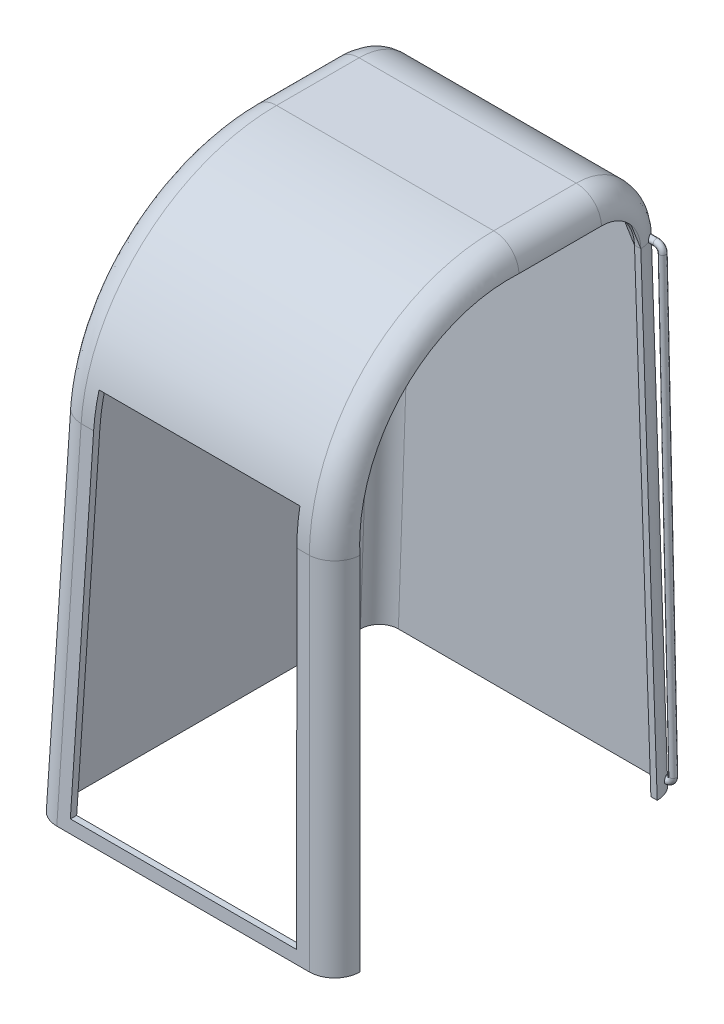
SolidWorks part; units mm, degrees
ref_plane "Front Plane" through (0, 0, 0) normal (0, 0, 1) x (1, 0, 0)
ref_plane "Top Plane" through (0, 0, 0) normal (0, 1, 0) x (1, 0, 0)
ref_plane "Right Plane" through (0, 0, 0) normal (1, 0, 0) x (0, 0, -1)
sketch "Sketch2" plane through (0, 0, 0) normal (0, 1, 0) x (1, 0, 0)
  line L1 (-533.4, -660.4) -> (533.4, -660.4)
  line L2 (-533.4, -660.4) -> (-533.4, 660.4)
  line L3 (-533.4, 660.4) -> (533.4, 660.4)
  line L4 (533.4, -660.4) -> (533.4, 660.4)
  line L5 (-533.4, -660.4) -> (533.4, 660.4) construction
  line L6 (-533.4, 660.4) -> (533.4, -660.4) construction
  point P0 (0, 0)
  dimension "D1" = 1320.8
  dimension "D2" = 1066.8
extrude "Boss-Extrude1" add sketch "Sketch2" along normal blind 2133.6
draft "Draft1" type of draft neutral plane draft angle 2 faces to draft 3 face at (533.4, 1066.8, 0) face at (-533.4, 1066.8, 0) face at (0, 1066.8, 660.4) neutral plane through (0, 2133.6, 0) neutral plane normal (0, 1, 0) parameters "D1"=2
fillet "Fillet3" radius 762 1 edges at (0, 2133.6, 660.4)
fillet "Fillet4" radius 254 1 edges at (0, 2133.6, -660.4)
fillet "Fillet5" radius 101.6 10 edges at (-583.494, 699.0967, 710.494) (-575.0884, 939.8, -660.4) (-535.9979, 2059.2051, -586.0051) (-533.4, 2133.6, -240.9274) (575.0884, 939.8, -660.4) (535.9979, 2059.2051, -586.0051) (533.4, 2133.6, -240.9274) (583.494, 699.0967, 710.494) (-540.8683, 1919.7369, 453.8748) (540.8683, 1919.7369, 453.8748)
shell "Shell2" thickness 25.4 removed face at (0, 0, 37.2676)
sketch "Sketch7" plane through (607.1665, 21.2027, 0) normal (0.9994, 0.0349, 0) x (0, 0, -1)
  line L0 (-584.5429, 1377.83) -> (-633.3688, -21.2156)
  line L1 (-633.3688, -21.2156) -> (558.8, -21.2156)
  line L2 (558.8, -21.2156) -> (558.8, 1863.078)
  line L3 (75.4548, 2015.5709) -> (406.4, 2015.5709)
  arc A0 (75.4548, 2015.5709) -> (-584.5429, 1377.83) centre (39.2865, 1392.6154) ccw
  arc A1 (406.4, 2015.5709) -> (558.8, 1863.078) centre (406.3071, 1863.078) cw
extrude "Cut-Extrude4" cut sketch "Sketch7" against normal blind 127
sketch "Sketch8" plane through (0, 25.6323, 734.0119) normal (0, 0.0349, 0.9994) x (1, 0, 0)
  line L0 (-451.9049, 1560.6151) -> (451.9049, 1560.6151)
  line L1 (451.9049, 1560.6151) -> (506.3688, -25.6479)
  line L3 (-506.3688, -25.6479) -> (-451.9049, 1560.6151)
  line L4 (-506.3688, -25.6479) -> (506.3688, -25.6479)
  line L5 (-453.7947, 25.1521) -> (-402.8192, 1509.8151)
  line L6 (-402.8192, 1509.8151) -> (402.8192, 1509.8151)
  line L7 (402.8192, 1509.8151) -> (453.7947, 25.1521)
  line L8 (-453.7947, 25.1521) -> (453.7947, 25.1521)
  spline S0 degree 3 poles (-435.286, 2134.9336) (-435.286, 2119.7833) (-444.4126, 1807.5095) (-457.5429, 1373.3978) knots 0 0 0 0 1 1 1 1 weights 1 0.812893 0.812893 1 construction
  spline S1 degree 3 poles (457.5429, 1373.3978) (444.4126, 1807.5095) (435.286, 2119.7833) (435.286, 2134.9336) knots 0 0 0 0 1 1 1 1 weights 1 0.812893 0.812893 1 construction
  line M5 (457.5429, 1373.3978) -> (-457.5429, 1373.3978)
  dimension "D1" = 50.8
extrude "Cut-Extrude5" cut sketch "Sketch8" against normal blind 127 contours L5 L8 L7 M5 | L7 L6 L5 M5 region at (0, 712.4114, 710.029) region at (0, 1466.2292, 683.7051)
ref_plane "Plane2" through (0, 0, -609.6) normal (0, 0, 1) x (1, 0, 0)
sketch "Sketch9" plane through (0, 0, -609.6) normal (0, 0, 1) x (1, 0, 0)
  line L1 (621.1963, 65.9357) -> (579.1358, 1861.2961)
  line L3 (553.7428, 1886.1012) -> (518.6241, 1886.1012)
  line L4 (595.8032, 39.9408) -> (579.1358, 39.9408)
  arc A0 (595.8032, 39.9408) -> (621.1963, 65.9357) centre (595.8032, 65.3408) ccw
  arc A1 (579.1358, 1861.2961) -> (553.7428, 1886.1012) centre (553.7428, 1860.7012) ccw
  dimension "D1" = 25.4
sweep "Sweep1" add path "Sketch9" circular profile diameter 25.4 parameters "D3"=25.4
ref_plane "Plane3" through (558.8, 0, 0) normal (1, 0, 0) x (0, 0, -1)
